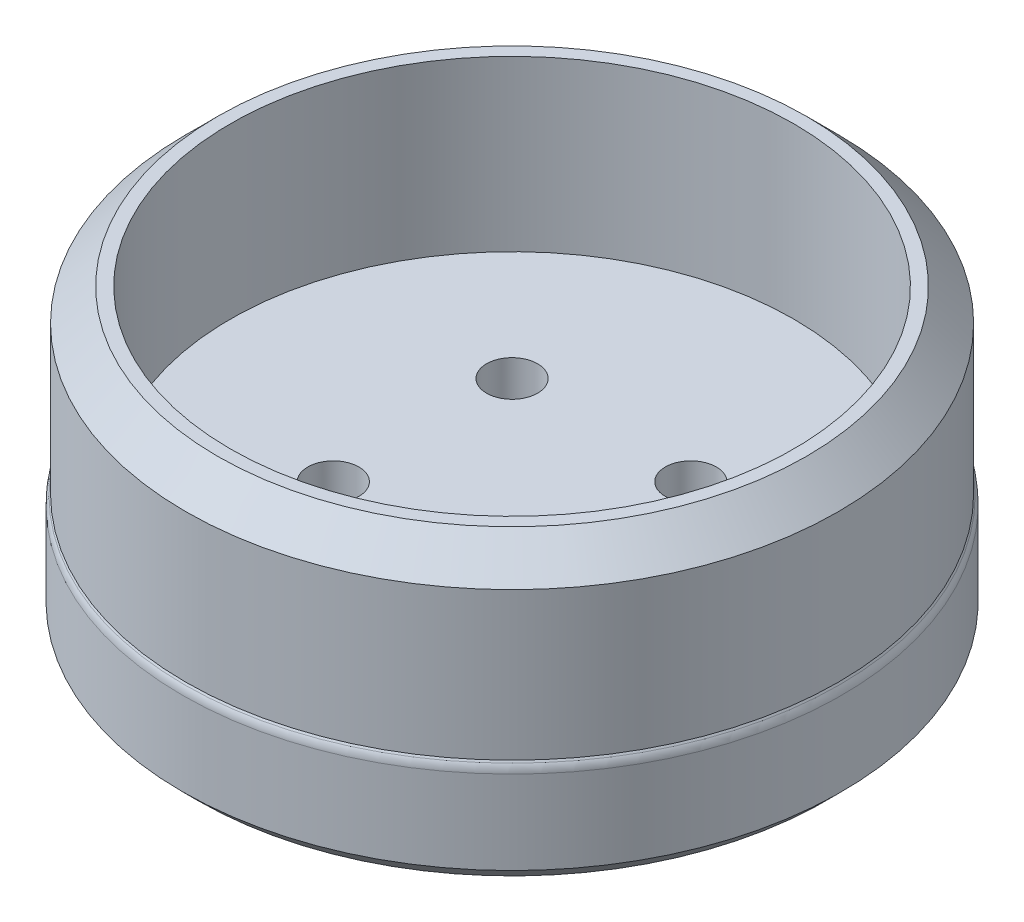
SolidWorks part; units mm, degrees
ref_plane "前视基准面" through (0, 0, 0) normal (0, 0, 1) x (1, 0, 0)
ref_plane "上视基准面" through (0, 0, 0) normal (0, 1, 0) x (1, 0, 0)
ref_plane "右视基准面" through (0, 0, 0) normal (1, 0, 0) x (0, 0, -1)
other "Configuration Table"
sketch "Sketch1" plane through (0, 0, 0) normal (0, 1, 0) x (1, 0, 0)
  circle A0 centre (0, 0) radius 20.65
  dimension "D1" = 41.3
extrude "Boss-Extrude1" add sketch "Sketch1" along normal blind 6.5 and the other way blind 1
sketch "Sketch2" plane through (0, 6.5, 0) normal (0, 1, 0) x (1, 0, 0)
  circle A0 centre (0, 0) radius 20.45
  circle A1 centre (0, 0) radius 17.65
  dimension "D1" = 2.8
  dimension "D2" = 35.3
extrude "Boss-Extrude2" add sketch "Sketch2" along normal blind 10.6
sketch "Sketch4" plane through (0, -1, 0) normal (0, -1, 0) x (1, 0, 0)
  line L1 (-5.6, 5.6) -> (5.6, 5.6)
  line L2 (-5.6, 5.6) -> (-5.6, -5.6)
  line L3 (-5.6, -5.6) -> (5.6, -5.6)
  line L4 (5.6, 5.6) -> (5.6, -5.6)
  line L5 (-5.6, 5.6) -> (5.6, -5.6) construction
  line L6 (-5.6, -5.6) -> (5.6, 5.6) construction
  circle A4 centre (-5.6, 5.6) radius 1.6
  circle A5 centre (5.6, 5.6) radius 1.6
  circle A6 centre (5.6, -5.6) radius 1.6
  circle A7 centre (-5.6, -5.6) radius 1.6
  point P0 (0, 0)
  point P17 (0, 0)
  dimension "D3" = 3.2
  dimension "D1" = 11.2
  dimension "D2" = 11.2
extrude "Cut-Extrude1" cut sketch "Sketch4" against normal blind 13.5 contours A4 | A7 | A6 | A5
sketch "Sketch8" plane through (0, -1, 0) normal (0, -1, 0) x (1, 0, 0)
  circle A4 centre (5.6, -5.6) radius 2.8
  circle A5 centre (-5.6, -5.6) radius 2.8
  circle A6 centre (-5.6, 5.6) radius 2.8
  circle A7 centre (5.6, 5.6) radius 2.8
  point P11 (0, 0)
  dimension "D1" = 5.6
extrude "Cut-Extrude2" cut sketch "Sketch8" against normal blind 2
chamfer "Chamfer1" distance 1 angle 45 1 edges at (0, -1, 20.65)
chamfer "Chamfer3" distance 1 angle 30 1 edges at (0, 6.5, 20.65) first distance on face at (0, 0, 20.65)
fillet "Fillet1" radius 1 1 edges at (0, 5.5, 20.65)
chamfer "Chamfer4" distance 2 angle 45 1 edges at (0, 17.1, 20.45)
